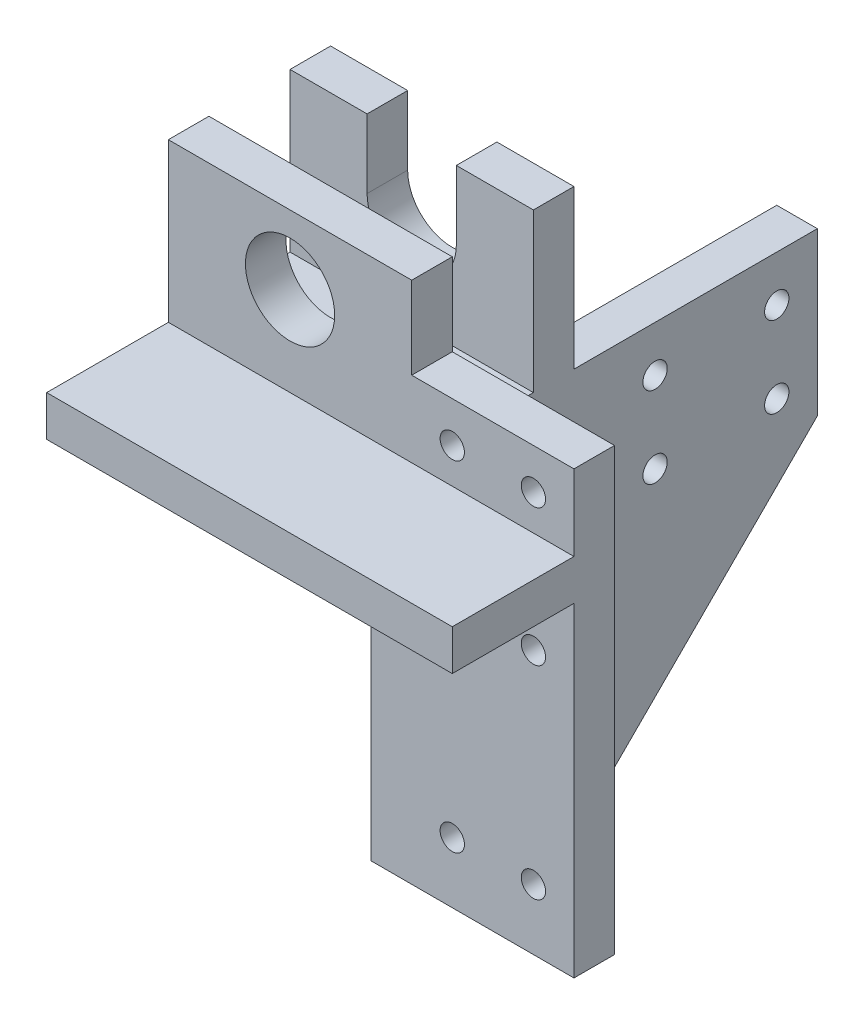
SolidWorks part; units mm, degrees
ref_plane "Front Plane" through (0, 0, 0) normal (0, 0, 1) x (1, 0, 0)
ref_plane "Top Plane" through (0, 0, 0) normal (0, 1, 0) x (1, 0, 0)
ref_plane "Right Plane" through (0, 0, 0) normal (1, 0, 0) x (0, 0, -1)
sketch "Sketch1" plane through (0, 0, 0) normal (0, 1, 0) x (1, 0, 0)
  line L0 (0, 0) -> (100, 0)
  line L1 (100, 0) -> (100, 40)
  line L2 (100, 40) -> (60, 40)
  line L3 (60, 40) -> (60, 80)
  line L4 (60, 80) -> (0, 80)
  line L5 (0, 80) -> (0, 0)
  dimension "D1" = 40
  dimension "D2" = 40
  dimension "D3" = 100
  dimension "D4" = 40
extrude "Boss-Extrude1" add sketch "Sketch1" along normal blind 10
sketch "Sketch2" plane through (0, 0, 0) normal (0, -1, 0) x (1, 0, 0)
  line L0 (60, -40) -> (100, -40)
  line L1 (100, -40) -> (100, -30)
  line L2 (100, 0) -> (100, -40) construction
  line L3 (100, -30) -> (50, -30)
  line L4 (50, -30) -> (50, -80)
  line L5 (60, -80) -> (0, -80) construction
  line L6 (50, -80) -> (60, -80)
  line L7 (60, -80) -> (60, -40)
  dimension "D1" = 10
  dimension "D2" = 10
extrude "Boss-Extrude2" add sketch "Sketch2" along normal blind 80
sketch "Sketch3" plane through (0, 10, 0) normal (0, 1, 0) x (1, 0, 0)
  line L0 (60, 40) -> (60, 80) construction
  line L1 (100, 40) -> (60, 40)
  line L2 (100, 40) -> (100, 30)
  line L3 (100, 30) -> (60, 30)
  line L4 (60, 40) -> (60, 30)
  dimension "D1" = 10
extrude "Boss-Extrude3" add sketch "Sketch3" along normal blind 18.71
sketch "Sketch4" plane through (0, 0, -80) normal (0, 0, -1) x (-1, 0, 0)
  line L0 (-60, 10) -> (-60, -80)
  line L1 (-60, 10) -> (-60, -80) construction
  line L2 (-60, -80) -> (-50, -80)
  line L3 (-50, -80) -> (-50, 0) construction
  line L4 (-50, -80) -> (-50, 10)
  line L5 (-60, 10) -> (0, 10) construction
  line L6 (-50, 10) -> (-60, 10)
  line L7 (-50, -80) -> (-60, -80) construction
extrude "Boss-Extrude4" add sketch "Sketch4" along normal blind 50
sketch "Sketch5" plane through (50, 0, 0) normal (-1, 0, 0) x (0, 0, 1)
  line L0 (-80, 10) -> (-80, -80) construction
  line L1 (-30, -80) -> (-130, -80) construction
  line L2 (-80, -80) -> (-130, -30)
  line L3 (-130, -80) -> (-130, 10) construction
  line L7 (-130, -30) -> (-130, -80)
  line L8 (-130, -80) -> (-80, -80)
  dimension "D1" = 50
extrude "Cut-Extrude1" cut sketch "Sketch5" against normal up to next
sketch "Sketch6" plane through (0, 10, 0) normal (0, 1, 0) x (1, 0, 0)
  line L0 (50, 80) -> (0, 80) construction
  line L1 (0, 80) -> (0, 0) construction
  circle A0 centre (7, 50) radius 3.5
  circle A1 centre (53, 50) radius 3.5
  dimension "D1" = 7
  dimension "D2" = 30
  dimension "D3" = 7
  dimension "D4" = 46
extrude "Cut-Extrude2" cut sketch "Sketch6" against normal blind 10
sketch "Sketch7" plane through (50, 0, 0) normal (-1, 0, 0) x (0, 0, 1)
  line L0 (-50, 0) -> (-43, 0)
  line L1 (-48.1972, 0) -> (-51.8028, 0) construction
  line L2 (-80, 0) -> (0, 0) construction
  line L3 (-43, 0) -> (-43, -6)
  line L4 (-43, -6) -> (-57, -6)
  line L5 (-57, -6) -> (-57, 0)
  line L6 (-57, 0) -> (-50, 0)
  dimension "D1" = 14
  dimension "D2" = 7
  dimension "D3" = 6
extrude "Cut-Extrude3" cut sketch "Sketch7" against normal blind 10
sketch "Sketch8" plane through (0, 0, -30) normal (0, 0, 1) x (1, 0, 0)
  line L0 (60, 28.71) -> (100, 28.71) construction
  line L1 (100, 28.71) -> (100, 10) construction
  line L3 (100, -80) -> (50, -80) construction
  circle A0 centre (70, 18.71) radius 3
  circle A1 centre (90, 18.71) radius 3
  circle A2 centre (70, -15) radius 3
  circle A3 centre (90, -15) radius 3
  circle A4 centre (90, -65) radius 3
  circle A5 centre (70, -65) radius 3
  dimension "D4" = 6
  dimension "D1" = 10
  dimension "D2" = 10
  dimension "D3" = 20
  dimension "D5" = 50
  dimension "D6" = 15
extrude "Cut-Extrude4" cut sketch "Sketch8" against normal blind 10
sketch "Sketch9" plane through (50, 0, 0) normal (-1, 0, 0) x (0, 0, 1)
  line L0 (-30, -80) -> (-30, 0) construction
  line L1 (-80, 0) -> (0, 0) construction
  line L2 (-30, -80) -> (-80, -80) construction
  line L3 (-130, 10) -> (-80, 10) construction
  line L4 (-130, -30) -> (-130, 10) construction
  circle A0 centre (-50, -15) radius 3
  circle A1 centre (-70, -15) radius 3
  circle A2 centre (-70, -65) radius 3
  circle A3 centre (-50, -65) radius 3
  circle A4 centre (-90, -1.3) radius 3
  circle A5 centre (-120, -1.3) radius 3
  circle A6 centre (-90, -21.3) radius 3
  circle A7 centre (-120, -21.3) radius 3
  dimension "D1" = 6
  dimension "D2" = 20
  dimension "D3" = 20
  dimension "D4" = 15
  dimension "D5" = 15
  dimension "D6" = 11.3
  dimension "D7" = 20
  dimension "D8" = 10
  dimension "D9" = 30
extrude "Cut-Extrude5" cut sketch "Sketch9" against normal blind 10
sketch "Sketch10" plane through (0, 10, 0) normal (0, 1, 0) x (1, 0, 0)
  line L0 (0, 80) -> (0, 0) construction
  line L1 (0, 40) -> (60, 40)
  line L2 (0, 40) -> (0, 30)
  line L3 (0, 30) -> (60, 30)
  line L4 (60, 40) -> (60, 30)
  line L5 (60, 40) -> (60, 30) construction
  line L6 (0, 0) -> (100, 0) construction
  line L7 (60, 40) -> (60, 130) construction
  line L8 (0, 70) -> (60, 70)
  line L9 (0, 70) -> (0, 60)
  line L10 (0, 60) -> (60, 60)
  line L11 (60, 70) -> (60, 60)
  dimension "D1" = 10
  dimension "D2" = 30
  dimension "D3" = 10
  dimension "D4" = 20
extrude "Boss-Extrude5" add sketch "Sketch10" along normal blind 39
sketch "Sketch11" plane through (0, 0, -30) normal (0, 0, 1) x (1, 0, 0)
  line L0 (0, 10) -> (100, 10) construction
  line L1 (0, 49) -> (0, 10) construction
  circle A0 centre (30, 32) radius 11
  dimension "D2" = 22
  dimension "D1" = 22
  dimension "D3" = 30
extrude "Cut-Extrude6" cut sketch "Sketch11" against normal blind 10
sketch "Sketch12" plane through (0, 0, -70) normal (0, 0, -1) x (-1, 0, 0)
  line L0 (-19, 49) -> (-19, 32)
  line L1 (-60, 49) -> (0, 49) construction
  line L2 (-19, 49) -> (-41, 49)
  line L3 (-41, 49) -> (-41, 32)
  line L4 (0, 49) -> (0, 10) construction
  line L5 (-60, 10) -> (0, 10) construction
  arc A0 (-19, 32) -> (-41, 32) centre (-30, 32) cw
  point P8 (-30, 49)
  dimension "D4" = 11
  dimension "D1" = 22
  dimension "D2" = 30
  dimension "D3" = 30
  dimension "D5" = 22
extrude "Cut-Extrude7" cut sketch "Sketch12" against normal blind 10
